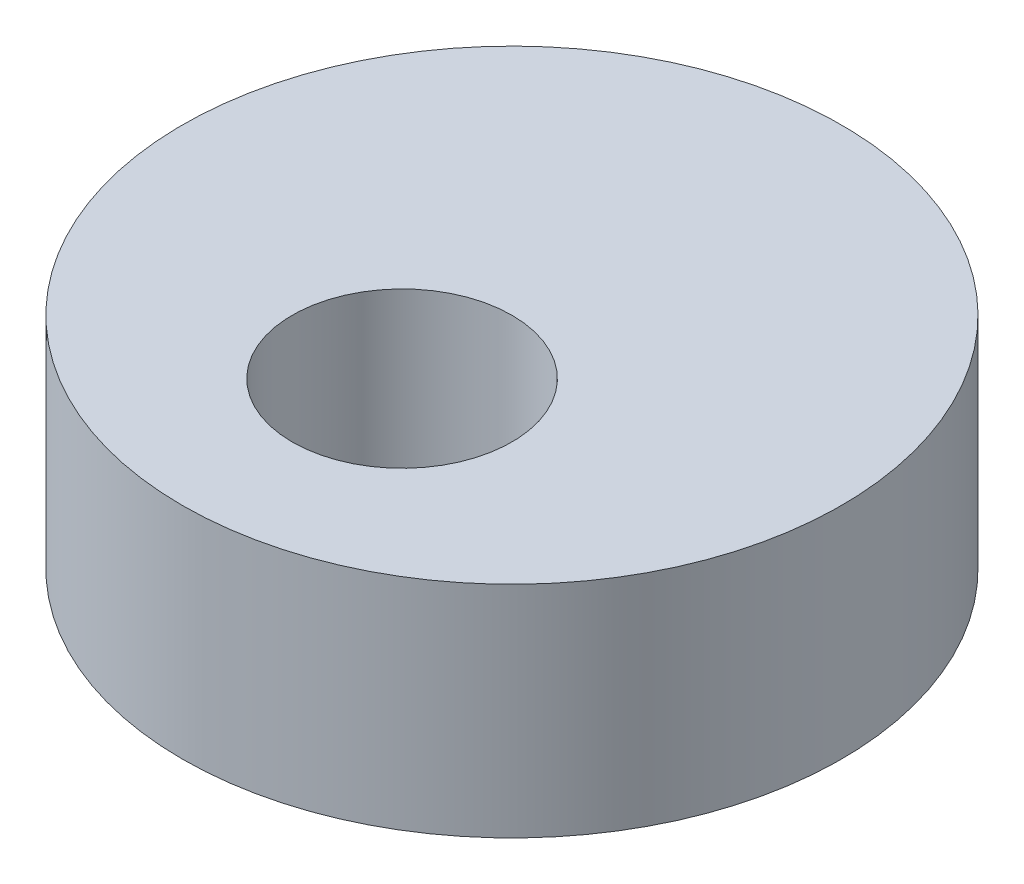
SolidWorks part; units mm, degrees
ref_plane "Front Plane" through (0, 0, 0) normal (0, 0, 1) x (1, 0, 0)
ref_plane "Top Plane" through (0, 0, 0) normal (0, 1, 0) x (1, 0, 0)
ref_plane "Right Plane" through (0, 0, 0) normal (1, 0, 0) x (0, 0, -1)
sketch "Sketch1" plane through (0, 0, 0) normal (0, 1, 0) x (1, 0, 0)
  line L0 (0, -3.175) -> (0, 0) construction
  circle A0 centre (0, 0) radius 9.525
  circle A1 centre (0, -3.175) radius 3.175
  dimension "D1" = 19.05
  dimension "D2" = 6.35
  dimension "D3" = 3.175
extrude "Boss-Extrude1" add sketch "Sketch1" along normal blind 6.35
equation "\"R\"= 1.5in'radius of rotor"
equation "\"E\"= .125in'eccentricity"
equation "\"R_r\"= .125in'radius of roller"
equation "\"N\"= 14'number of rollers"
equation "\"R_o\"= .2in'output disk pin diameter"
equation "\"D3@Sketch1\"=\"E\""
